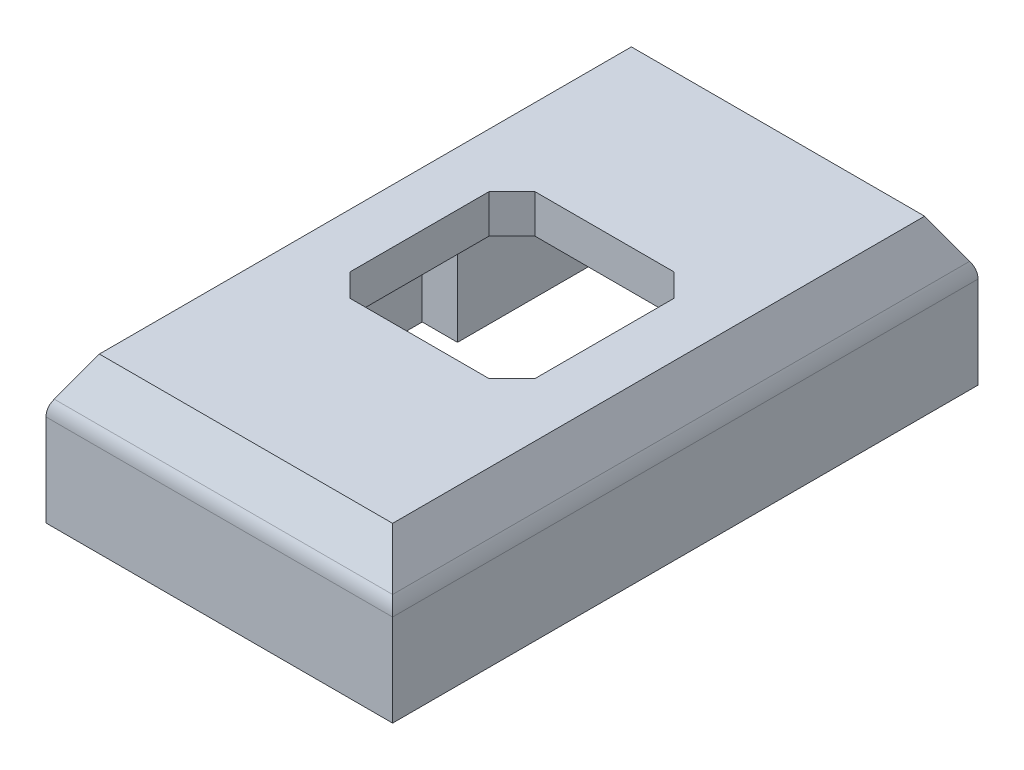
SolidWorks part; units mm, degrees
ref_plane "Front Plane" through (0, 0, 0) normal (0, 0, 1) x (1, 0, 0)
ref_plane "Top Plane" through (0, 0, 0) normal (0, 1, 0) x (1, 0, 0)
ref_plane "Right Plane" through (0, 0, 0) normal (1, 0, 0) x (0, 0, -1)
sketch "Sketch1" plane through (0, 0, 0) normal (0, 1, 0) x (1, 0, 0)
  line L0 (-8.05, 15.8) -> (-8.05, -15.8)
  line L1 (-11.25, 19) -> (11.25, 19)
  line L2 (-11.25, 19) -> (-11.25, -19)
  line L3 (-11.25, -19) -> (11.25, -19)
  line L4 (11.25, 19) -> (11.25, -19)
  line L5 (-11.25, 19) -> (11.25, -19) construction
  line L6 (-11.25, -19) -> (11.25, 19) construction
  line L7 (-8.05, -15.8) -> (8.05, -15.8)
  line L8 (8.05, 15.8) -> (8.05, -15.8)
  line L9 (-8.05, 15.8) -> (8.05, 15.8)
  line L10 (-8.05, 0) -> (-8.05, -4.4929)
  line L11 (-8.05, 0) -> (-10.3379, 0)
  line L12 (-8.05, -4.4929) -> (-10.3379, -4.4929)
  line L13 (-10.3379, 0) -> (-10.3379, -4.4929)
  line L14 (-10.3379, 0) -> (-10.3379, 4.5118)
  line L15 (-10.3379, 0) -> (-7.9379, 0)
  line L16 (-10.3379, 4.5118) -> (-7.9379, 4.5118)
  line L17 (-7.9379, 0) -> (-7.9379, 4.5118)
  line L18 (8.05, 0) -> (10.3147, 0)
  line L19 (8.05, 0) -> (8.05, 4.4948)
  line L20 (10.3147, 0) -> (10.3147, 4.4948)
  line L21 (8.05, 4.4948) -> (10.3147, 4.4948)
  line L22 (8.05, 0) -> (10.3147, 0)
  line L23 (8.05, 0) -> (8.05, -4.4266)
  line L24 (10.3147, 0) -> (10.3147, -4.4266)
  line L25 (8.05, -4.4266) -> (10.3147, -4.4266)
  point P0 (0, 0)
  dimension "D1" = 3.2
extrude "Boss-Extrude2" add sketch "Sketch1" along normal blind 7 contours L4 L1 L2 L3 L25 L8 L7 L0 L12 L13 L14 L16 L9 L21 L20 L24 region at (0, 0, -18.5584)
sketch "Sketch2" plane through (0, 7, 0) normal (0, 1, 0) x (1, 0, 0)
  line L1 (-11.25, 19) -> (11.25, 19)
  line L2 (-11.25, 19) -> (-11.25, -19)
  line L3 (-11.25, -19) -> (11.25, -19)
  line L4 (11.25, 19) -> (11.25, -19)
  line L5 (-11.25, 19) -> (11.25, -19) construction
  line L6 (-11.25, -19) -> (11.25, 19) construction
  point P0 (0, 0)
extrude "Boss-Extrude4" add sketch "Sketch2" along normal blind 2.5
sketch "Sketch3" plane through (0, 9.5, 0) normal (0, 1, 0) x (1, 0, 0)
  line L1 (-6, 6) -> (6, 6)
  line L2 (-6, 6) -> (-6, -6)
  line L3 (-6, -6) -> (6, -6)
  line L4 (6, 6) -> (6, -6)
  line L5 (-6, 6) -> (6, -6) construction
  line L6 (-6, -6) -> (6, 6) construction
  point P0 (0, 0)
extrude "Cut-Extrude1" cut sketch "Sketch3" against normal blind 2.5
chamfer "Chamfer1" distance 1.5 angle 45 4 edges at (6, 8.25, 6) (-6, 8.25, 6) (-6, 8.25, -6) (6, 8.25, -6)
fillet "Fillet3" radius 2 12 edges at (8.05, 7, -10.1474) (0, 7, -15.8) (-8.05, 7, -10.1559) (-9.194, 7, -4.5118) (-9.194, 7, 4.4929) (-8.05, 7, 10.1465) (-8.05, 3.5, 15.8) (0, 7, 15.8) (8.05, 3.5, 15.8) (8.05, 7, 10.1133) (9.1823, 7, 4.4266) (9.1823, 7, -4.4948)
fillet "Fillet4" radius 2 4 edges at (-7.4642, 6.4142, -15.2142) (7.4642, 6.4142, -15.2142) (-8.05, 2.5, -15.8) (8.05, 2.5, -15.8)
chamfer "Chamfer2" distance 3 angle 30 4 edges at (-11.25, 9.5, 0) (0, 9.5, -19) (11.25, 9.5, 0) (0, 9.5, 19) first distance on face at (-11.25, 4.75, 0) first distance on face at (0, 4.75, -19) first distance on face at (11.25, 4.75, 0) first distance on face at (0, 4.75, 19)
fillet "Fillet5" radius 2 4 edges at (11.25, 6.5, 0) (0, 6.5, 19) (-11.25, 6.5, 0) (0, 6.5, -19)
